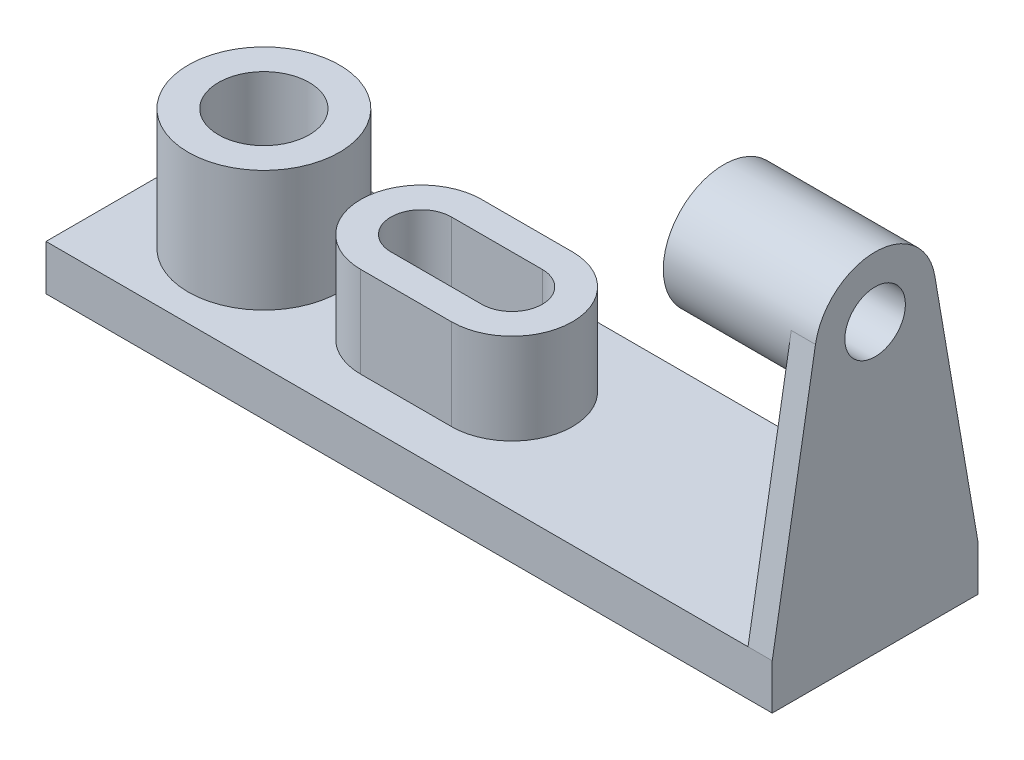
SolidWorks part; units mm, degrees
ref_plane "Front Plane" through (0, 0, 0) normal (0, 0, 1) x (1, 0, 0)
ref_plane "Top Plane" through (0, 0, 0) normal (0, 1, 0) x (1, 0, 0)
ref_plane "Right Plane" through (0, 0, 0) normal (1, 0, 0) x (0, 0, -1)
sketch "Sketch2" plane through (0, 0, 0) normal (0, 1, 0) x (1, 0, 0)
  line L0 (-82, 0) -> (-120, 0) construction
  line L1 (-120, 34) -> (120, 34)
  line L2 (-120, 34) -> (-120, -34)
  line L3 (-120, -34) -> (120, -34)
  line L4 (120, 34) -> (120, -34)
  line L5 (-120, 34) -> (120, -34) construction
  line L6 (-120, -34) -> (120, 34) construction
  circle A0 centre (-82, 0) radius 25
  circle A1 centre (-82, 0) radius 15
  point P0 (0, 0)
  dimension "D1" = 50
  dimension "D4" = 30
  dimension "D2" = 68
  dimension "D3" = 240
  dimension "D5" = 202
extrude "Boss-Extrude1" add sketch "Sketch2" against normal blind 15 contours L4 L1 L2 L3 A0 region at (11.2149, 0, 0)
extrude "Boss-Extrude3" add sketch "Sketch2<4>" along normal blind 40 separate body contours A0
sketch "Sketch2<4>" plane through (0, 0, 0) normal (0, 1, 0) x (1, 0, 0) same geometry as "Sketch2"
extrude "Cut-Extrude1" cut sketch "Sketch2<5>" along normal blind 52 contours A1
sketch "Sketch2<5>" plane through (0, 0, 0) normal (0, 1, 0) x (1, 0, 0) same geometry as "Sketch2"
sketch "Sketch4" plane through (0, 0, 0) normal (0, 1, 0) x (1, 0, 0)
  line L0 (-82, 0) -> (120, 0) construction
  line L1 (120, 34) -> (120, -34) construction
  line L2 (-30, 0) -> (0, 0) construction
  line L3 (-30, 20) -> (0, 20)
  line L4 (-30, -20) -> (0, -20)
  line L5 (-30, 10) -> (0, 10)
  line L6 (-30, -10) -> (0, -10)
  arc A0 (-30, 20) -> (-30, -20) centre (-30, 0) ccw
  arc A1 (0, -20) -> (0, 20) centre (0, 0) ccw
  arc A2 (0, -10) -> (0, 10) centre (0, 0) ccw
  arc A3 (-30, 10) -> (-30, -10) centre (-30, 0) ccw
  point P8 (-15, 0)
  dimension "D1" = 20
  dimension "D2" = 30
  dimension "D3" = 135
  dimension "D4" = 10
extrude "Boss-Extrude6" add sketch "Sketch4" along normal blind 30
sketch "Sketch6" plane through (0, 0, 0) normal (0, 1, 0) x (1, 0, 0)
  line L2 (-30, -10) -> (0, -10)
  line L3 (0, 10) -> (-30, 10)
  line L4 (-30, -10) -> (0, -10)
  line L5 (0, 10) -> (-30, 10)
  arc A2 (-30, 10) -> (-30, -10) centre (-30, 0) ccw
  arc A3 (0, -10) -> (0, 10) centre (0, 0) ccw
  arc A4 (-30, 10) -> (-30, -10) centre (-30, 0) ccw
  arc A5 (0, -10) -> (0, 10) centre (0, 0) ccw
  dimension "D1" = 0
extrude "Cut-Extrude3" cut sketch "Sketch6" against normal blind 30 and the other way blind 30
sketch "Sketch8" plane through (0, 0, 0) normal (0, 0, 1) x (1, 0, 0)
  line L0 (-57, 20) -> (-50, 20)
  line L1 (-57, 20) -> (-57, 0)
  line L2 (-57, 0) -> (-50, 0)
  line L3 (-50, 0) -> (-50, 20)
  line L4 (-57, 0) -> (-57, 40) construction
  line L5 (-50, 30) -> (-50, 0) construction
  dimension "D1" = 20
sketch "Sketch9" plane through (120, 0, 0) normal (1, 0, 0) x (0, 0, -1)
  line L0 (0, 0) -> (0, 75.7033) construction
  line L1 (0, 75.7033) -> (0, 80) construction
  line L2 (-34, 0) -> (-19.7127, 83.3779)
  line L6 (19.7378, 83.2278) -> (34, 0)
  line L7 (-34, 0) -> (34, 0)
  line L8 (34, -15) -> (-34, -15) construction
  arc A0 (19.7378, 83.2278) -> (-19.7127, 83.3779) centre (0, 80) ccw
  circle A1 centre (0, 80) radius 10
  dimension "D1" = 20
  dimension "D3" = 20
  dimension "D2" = 95
extrude "Boss-Extrude7" add sketch "Sketch9" against normal blind 8
sketch "Sketch10" plane through (112, 0, 0) normal (-1, 0, 0) x (0, 0, 1)
  circle A0 centre (0, 80) radius 20
  circle A1 centre (0, 80) radius 10
extrude "Boss-Extrude8" add sketch "Sketch10" along normal blind 42
sketch "Sketch11" plane through (0, 0, 0) normal (0, 0, 1) x (1, 0, 0)
  line L0 (81.641, 60) -> (47, 0)
  line L1 (70, 60) -> (112, 60) construction
  line L2 (-120, 0) -> (120, 0) construction
  line L3 (-120, 0) -> (120, 0) construction
  line L4 (47, 0) -> (112, 0)
  line L5 (112, 0) -> (112, 60)
  line L6 (112, 83.3779) -> (112, 0) construction
  line L7 (112, 60) -> (81.641, 60)
  dimension "D1" = 65
  dimension "D2" = 60
